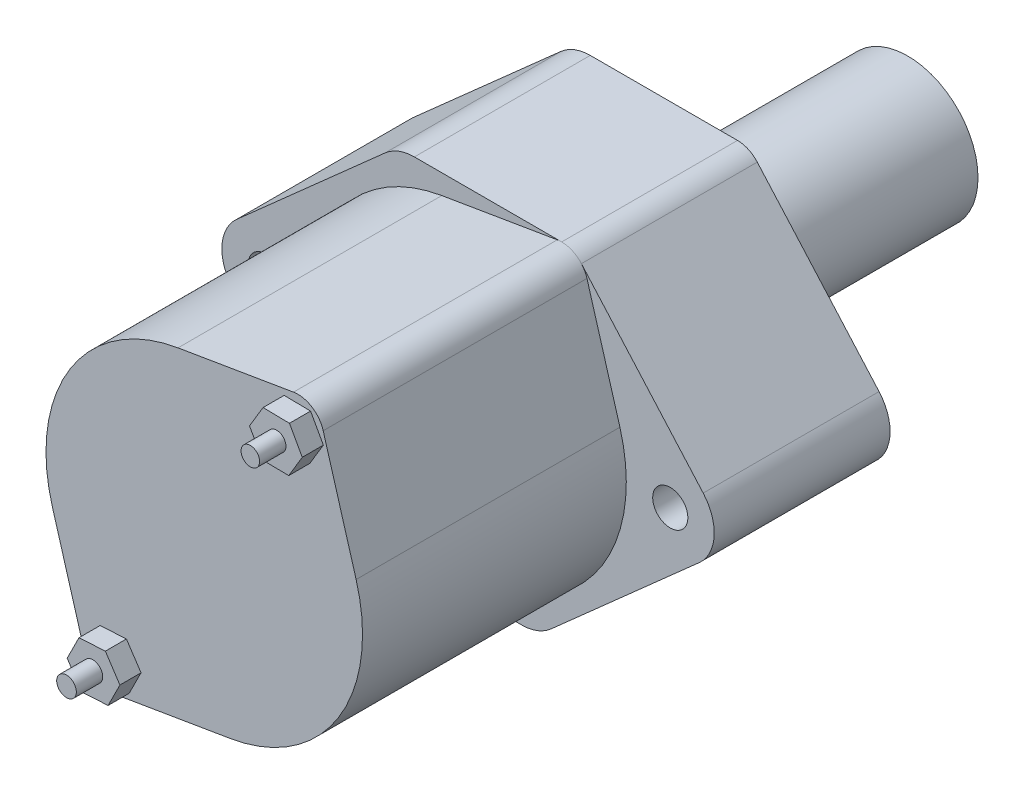
SolidWorks part; units mm, degrees
ref_plane "Спереди" through (0, 0, 0) normal (0, 0, 1) x (1, 0, 0)
ref_plane "Сверху" through (0, 0, 0) normal (0, 1, 0) x (1, 0, 0)
ref_plane "Справа" through (0, 0, 0) normal (1, 0, 0) x (0, 0, -1)
sketch "Эскиз1" plane through (0, 0, 0) normal (0, 0, 1) x (1, 0, 0)
  line L0 (1.6135, 17.607) -> (46.8209, 17.607) construction
  line L1 (9.5013, 7.607) -> (19.5013, 7.607)
  line L2 (15.5013, 30.806) -> (15.5013, 3.723) construction
  line L3 (11.5013, 27.607) -> (21.5013, 27.607)
  line L4 (9.5013, 7.607) -> (2.1279, 15.9516)
  line L5 (11.5013, 27.607) -> (2.3417, 19.4767)
  line L6 (21.5013, 27.607) -> (28.8747, 19.2624)
  line L7 (28.6609, 15.7373) -> (19.5013, 7.607)
  circle A0 centre (27.0013, 17.607) radius 1
  circle A1 centre (4.0013, 17.607) radius 1
  arc A2 (28.6609, 15.7373) -> (28.8747, 19.2624) centre (27.0013, 17.607) ccw
  arc A3 (2.3417, 19.4767) -> (2.1279, 15.9516) centre (4.0013, 17.607) ccw
  dimension "D3" = 5
  dimension "D4" = 10
  dimension "D1" = 23
  dimension "D6" = 10
  dimension "D2" = 2
  dimension "D5" = 10
  dimension "D7" = 6
  dimension "D8" = 6
extrude "Вытянуть1" add sketch "Эскиз1" along normal blind 10
sketch "Эскиз2" plane through (0, 0, 10) normal (0, 0, 1) x (1, 0, 0)
  line L0 (0.7522, 17.607) -> (31.0879, 17.607) construction
  line L1 (15.5013, 29.5645) -> (15.5013, 5.399) construction
  line L2 (9.5013, 7.607) -> (19.5013, 7.607) construction
  line L3 (21.5013, 27.607) -> (11.5013, 27.607) construction
  line L4 (11.5013, 27.607) -> (19.5013, 7.607) construction
  line L5 (2.1279, 15.9516) -> (9.5013, 7.607) construction
  line L6 (28.8747, 19.2624) -> (21.5013, 27.607) construction
  line L7 (22.2645, 26.529) -> (24.1378, 20.139)
  line L8 (14.0095, 26.4825) -> (20.5764, 27.5863)
  line L9 (6.8648, 15.0751) -> (8.7382, 8.685)
  line L10 (10.4262, 7.6278) -> (16.9931, 8.7315)
  circle A0 centre (4.0013, 17.607) radius 1 construction
  circle A1 centre (27.0013, 17.607) radius 1 construction
  arc A2 (14.0095, 26.4825) -> (6.8648, 15.0751) centre (15.5013, 17.607) ccw
  arc A3 (22.2645, 26.529) -> (20.5764, 27.5863) centre (20.8251, 26.107) ccw
  arc A4 (8.7382, 8.685) -> (10.4262, 7.6278) centre (10.1776, 9.107) ccw
  arc A5 (16.9931, 8.7315) -> (24.1378, 20.139) centre (15.5013, 17.607) ccw
  dimension "D1" = 18
extrude "Вытянуть2" add sketch "Эскиз2" along normal blind 15
sketch "Эскиз3" plane through (0, 0, 0) normal (0, 0, -1) x (-1, 0, 0)
  line L0 (-15.5013, 21.3757) -> (-15.5013, 13.0629) construction
  line L1 (-9.5013, 7.607) -> (-19.5013, 7.607) construction
  line L2 (-19.8749, 17.607) -> (-9.4218, 17.607) construction
  line L3 (-21.5013, 27.607) -> (-11.5013, 27.607) construction
  circle A0 centre (-15.5013, 17.607) radius 4
  circle A1 centre (-27.0013, 17.607) radius 1 construction
  circle A2 centre (-4.0013, 17.607) radius 1 construction
  dimension "D1" = 8
extrude "Вытянуть3" add sketch "Эскиз3" along normal blind 15
fillet "Скругление1" radius 1.5
fillet "Скругление2" radius 2.5
sketch "Эскиз8" plane through (0, 0, 25) normal (0, 0, 1) x (1, 0, 0)
  line L1 (20.0461, 27.162) -> (19.2747, 25.8754)
  line L2 (19.2747, 25.8754) -> (20.0033, 24.564)
  line L3 (20.0033, 24.564) -> (21.5033, 24.5392)
  line L4 (21.5033, 24.5392) -> (22.2747, 25.8259)
  line L5 (22.2747, 25.8259) -> (21.5461, 27.1373)
  line L6 (21.5461, 27.1373) -> (20.0461, 27.162)
  line L7 (11.0768, 10.6806) -> (9.5768, 10.5906)
  line L8 (9.5768, 10.5906) -> (8.9047, 9.2465)
  line L9 (8.9047, 9.2465) -> (9.7327, 7.9925)
  line L10 (9.7327, 7.9925) -> (11.2327, 8.0826)
  line L11 (11.2327, 8.0826) -> (11.9047, 9.4266)
  line L12 (11.9047, 9.4266) -> (11.0768, 10.6806)
  circle A0 centre (20.7747, 25.8506) radius 1.2992 construction
  circle A1 centre (10.4047, 9.3366) radius 1.3014 construction
extrude "Вытянуть4" add sketch "Эскиз8" along normal blind 1.2
sketch "Эскиз9" plane through (0, 0, 26.2) normal (0, 0, 1) x (1, 0, 0)
  circle A0 centre (20.8209, 25.9043) radius 0.5273
extrude "Вытянуть5" add sketch "Эскиз9" along normal blind 1.5
sketch "Эскиз10" plane through (0, 0, 26.2) normal (0, 0, 1) x (1, 0, 0)
  circle A0 centre (10.3678, 9.3407) radius 0.5583
extrude "Вытянуть6" add sketch "Эскиз10" along normal blind 1.5
